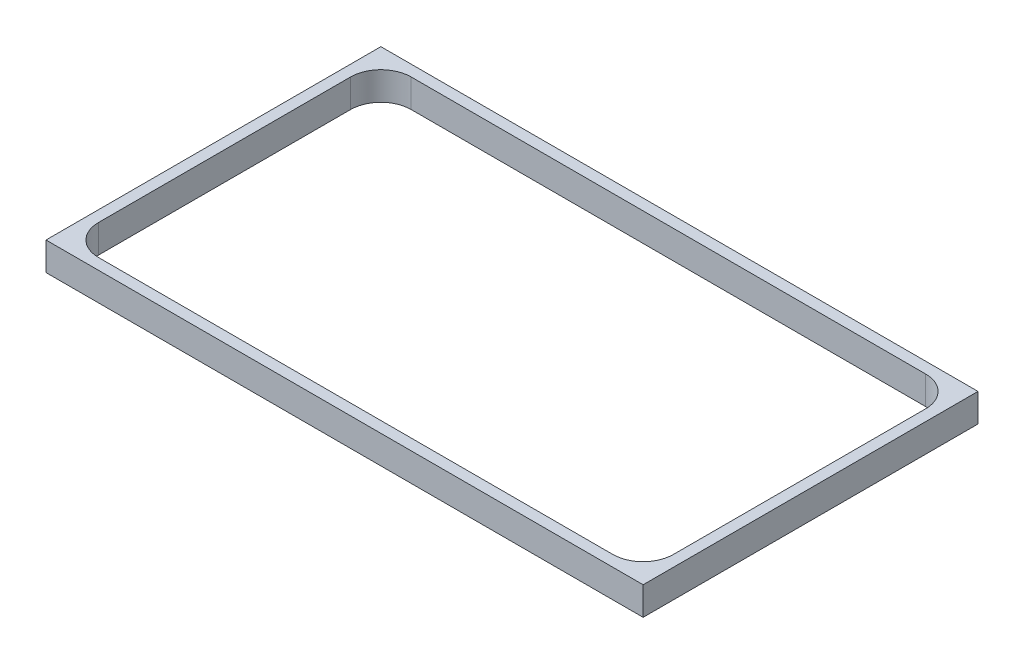
SolidWorks part; units mm, degrees
material "ABS"
ref_plane "Спереди" through (0, 0, 0) normal (0, 0, 1) x (1, 0, 0)
ref_plane "Сверху" through (0, 0, 0) normal (0, 1, 0) x (1, 0, 0)
ref_plane "Справа" through (0, 0, 0) normal (1, 0, 0) x (0, 0, -1)
sketch "Эскиз1" plane through (0, 0, 0) normal (0, 1, 0) x (1, 0, 0)
  line L0 (-61.2, 33.2) -> (57.2, 33.2)
  line L1 (57.2, 33.2) -> (57.2, -33.2)
  line L2 (-61.2, -33.2) -> (57.2, -33.2)
  line L3 (-59, 31) -> (55, 31)
  line L4 (-61.2, 33.2) -> (-61.2, -33.2)
  line L6 (-59, -31) -> (55, -31)
  line L7 (55, 31) -> (55, -31)
  line L12 (-59, 31) -> (-59, -31)
  point P0 (0, 0)
  dimension "D1" = 2.2
extrude "Бобышка-Вытянуть1" add sketch "Эскиз1" along normal blind 5.6
sketch "Эскиз5" plane through (0, 0, 0) normal (0, -1, 0) x (1, 0, 0)
  circle A0 centre (-54, 21) radius 3
  circle A1 centre (-54, -21) radius 3
  circle A2 centre (39, 21) radius 3
  circle A3 centre (39, -21) radius 3
extrude "под гайку" cut sketch "Эскиз5" against normal blind 3 rebuild error yes
sketch "Эскиз7" plane through (0, 0, 0) normal (0, -1, 0) x (1, 0, 0)
  line L6 (35, -29) -> (-50, -29)
  line L7 (35, -29) -> (35, 29)
  line L8 (35, 29) -> (-50, 29)
  line L9 (-50, -29) -> (-50, 29)
extrude "под LCD" cut sketch "Эскиз7" against normal blind 3.6 rebuild error yes
sketch "Эскиз11" plane through (0, 5.6, 0) normal (0, 1, 0) x (1, 0, 0)
  line L0 (-12.6056, 22.5401) -> (-12.6056, -41.5105) construction
sketch "Эскиз13" plane through (0, 3.6, 0) normal (0, -1, 0) x (1, 0, 0)
  line L4 (31, 23) -> (-43, 23)
  line L5 (31, 23) -> (31, -23)
  line L6 (31, -23) -> (-43, -23)
  line L7 (-43, 23) -> (-43, -23)
extrude "Вырез-Вытянуть1" cut sketch "Эскиз13" against normal blind 10 rebuild error yes
fillet "Скругление2" radius 5 rebuild error yes
fillet "Скругление3" radius 6 4 edges at (-59, 2.8, 31) (-59, 2.8, -31) (55, 2.8, 31) (55, 2.8, -31)
